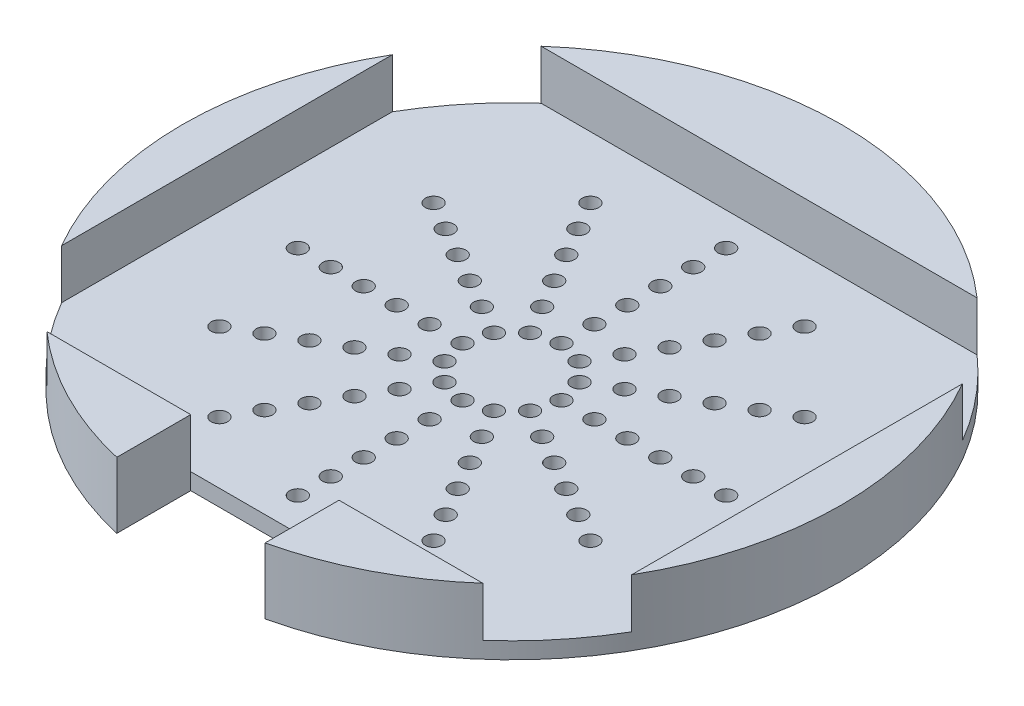
SolidWorks part; units mm, degrees
ref_plane "前基準面" through (0, 0, 0) normal (0, 0, 1) x (1, 0, 0)
ref_plane "上基準面" through (0, 0, 0) normal (0, 1, 0) x (1, 0, 0)
ref_plane "右基準面" through (0, 0, 0) normal (1, 0, 0) x (0, 0, -1)
sketch "草圖1" plane through (0, 0, 0) normal (0, 1, 0) x (1, 0, 0)
  circle A0 centre (0, 0) radius 100
  dimension "D1" = 200
extrude "填料-伸長1" add sketch "草圖1" along normal blind 20
sketch "草圖2" plane through (0, 20, 0) normal (0, 1, 0) x (1, 0, 0)
  line L1 (-86.5, -75) -> (86.5, -75)
  line L2 (-86.5, -75) -> (-86.5, 75)
  line L3 (-86.5, 75) -> (86.5, 75)
  line L4 (86.5, -75) -> (86.5, 75)
  line L5 (-86.5, -75) -> (86.5, 75) construction
  line L6 (-86.5, 75) -> (86.5, -75) construction
  point P0 (0, 0)
  dimension "D1" = 150
  dimension "D2" = 173
extrude "除料-伸長1" cut sketch "草圖2" against normal blind 15
sketch "草圖3" plane through (0, 5, 0) normal (0, 1, 0) x (1, 0, 0)
  line L0 (0, 0) -> (0, 75) construction
  line L1 (66.1438, 75) -> (-66.1438, 75) construction
  circle A0 centre (0, 65) radius 2.5
  circle A1 centre (0, 55) radius 2.5
  circle A2 centre (0, 45) radius 2.5
  circle A3 centre (0, 35) radius 2.5
  circle A4 centre (0, 25) radius 2.5
  circle A5 centre (0, 15) radius 2.5
  dimension "D1" = 5
  dimension "D3" = 10
  dimension "D4" = 10
  dimension "D5" = 10
  dimension "D6" = 10
  dimension "D7" = 10
  dimension "D2" = 10
extrude "除料-伸長2" cut sketch "草圖3" against normal through all
ref_axis "基準軸1" through (0, 20, 0) along (0, -1, 0)
pattern_circular "環狀複製排列2" count 12 every 30 about axis through (0, 20, 0) along (0, -1, 0) of "除料-伸長2"
sketch "草圖4" plane through (0, 20, 0) normal (0, 1, 0) x (1, 0, 0)
  line L0 (-66.1438, -75) -> (66.1438, -75) construction
  line L1 (-22.5, -75) -> (22.5, -75)
  line L2 (-22.5, -75) -> (-22.5, -100)
  line L3 (-22.5, -100) -> (22.5, -100)
  line L4 (22.5, -75) -> (22.5, -100)
  line L5 (0, -75) -> (0, 0) construction
  arc A0 (-66.1438, -75) -> (66.1438, -75) centre (0, 0) ccw construction
  point P10 (0, -75)
  dimension "D1" = 45
extrude "除料-伸長3" cut sketch "草圖4" against normal through all
